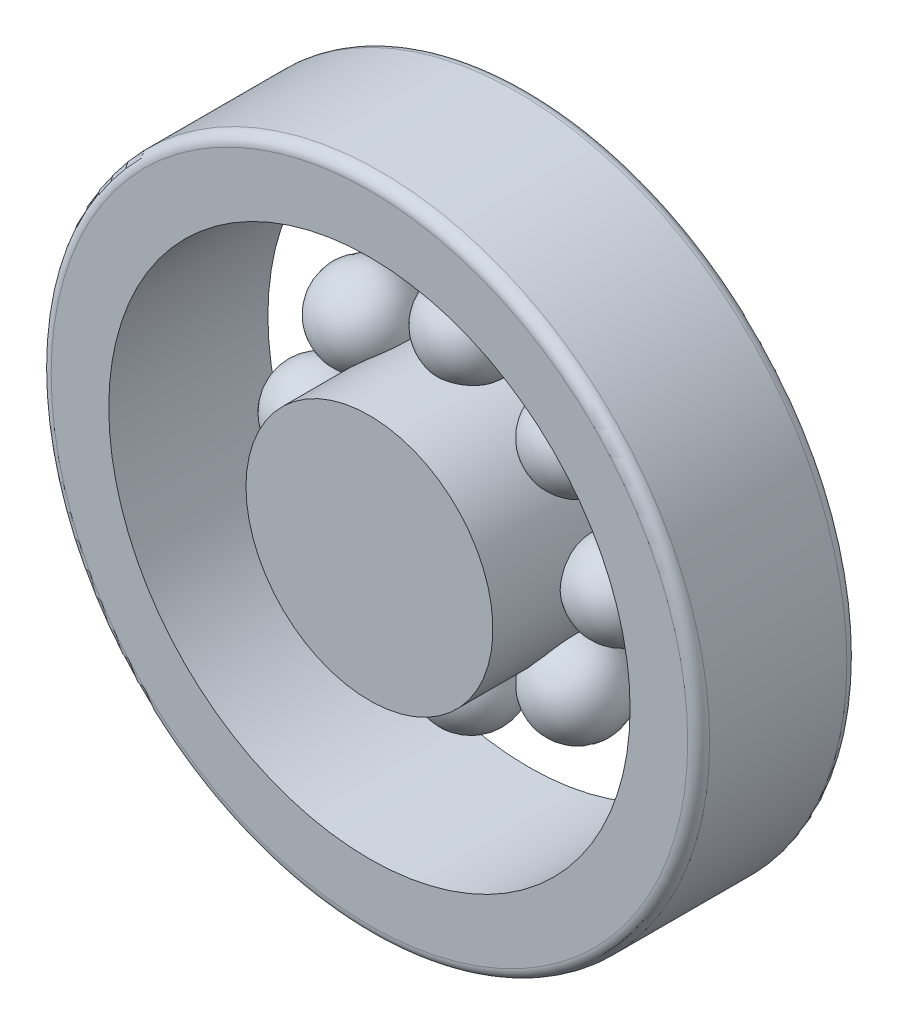
SolidWorks part; units mm, degrees
ref_plane "Front Plane" through (0, 0, 0) normal (0, 0, 1) x (1, 0, 0)
ref_plane "Top Plane" through (0, 0, 0) normal (0, 1, 0) x (1, 0, 0)
ref_plane "Right Plane" through (0, 0, 0) normal (1, 0, 0) x (0, 0, -1)
sketch "Sketch1" plane through (0, 0, 0) normal (0, 0, 1) x (1, 0, 0)
  circle A0 centre (0, 0) radius 35
  circle A1 centre (0, 0) radius 22.5
  circle A2 centre (0, 0) radius 47.5
  circle A3 centre (0, 0) radius 60
  dimension "D1" = 120
  dimension "D2" = 95
  dimension "D3" = 45
  dimension "D4" = 70
extrude "Boss-Extrude1" add sketch "Sketch1" along normal blind 29 contours A3 A2 | A1 A0 region at (0, 0, 0) region at (-58.3029, 0, 0)
sketch "Sketch2" plane through (0, 0, 0) normal (0, 1, 0) x (1, 0, 0)
  line L0 (22.5, -14.5) -> (47.5, -14.5) construction
  line L1 (22.5, -29) -> (22.5, 0) construction
  line L2 (47.5, -29) -> (47.5, 0) construction
  line L3 (0, 0) -> (0, 21.9554) construction
  circle A0 centre (35, -14.5) radius 9
  dimension "D1" = 18
revolve "Cut-Revolve1" cut sketch "Sketch2" angle 360 about L3 rebuild error yes
sketch "Sketch3" plane through (0, 0, 0) normal (0, 1, 0) x (1, 0, 0)
  line L0 (27.5, -2.5) -> (27.5, -18.5)
  arc A0 (27.5, -18.5) -> (27.5, -2.5) centre (27.5, -10.5) ccw
  point P1 (0, 0)
  dimension "D1" = 16
revolve "Revolve1" add sketch "Sketch3" angle 360 about L0
pattern_circular "CirPattern1" count 8 over 360 of bodies 105
fillet "Fillet1" radius 2 2 edges at (60, 0, 29) (60, 0, 0)
